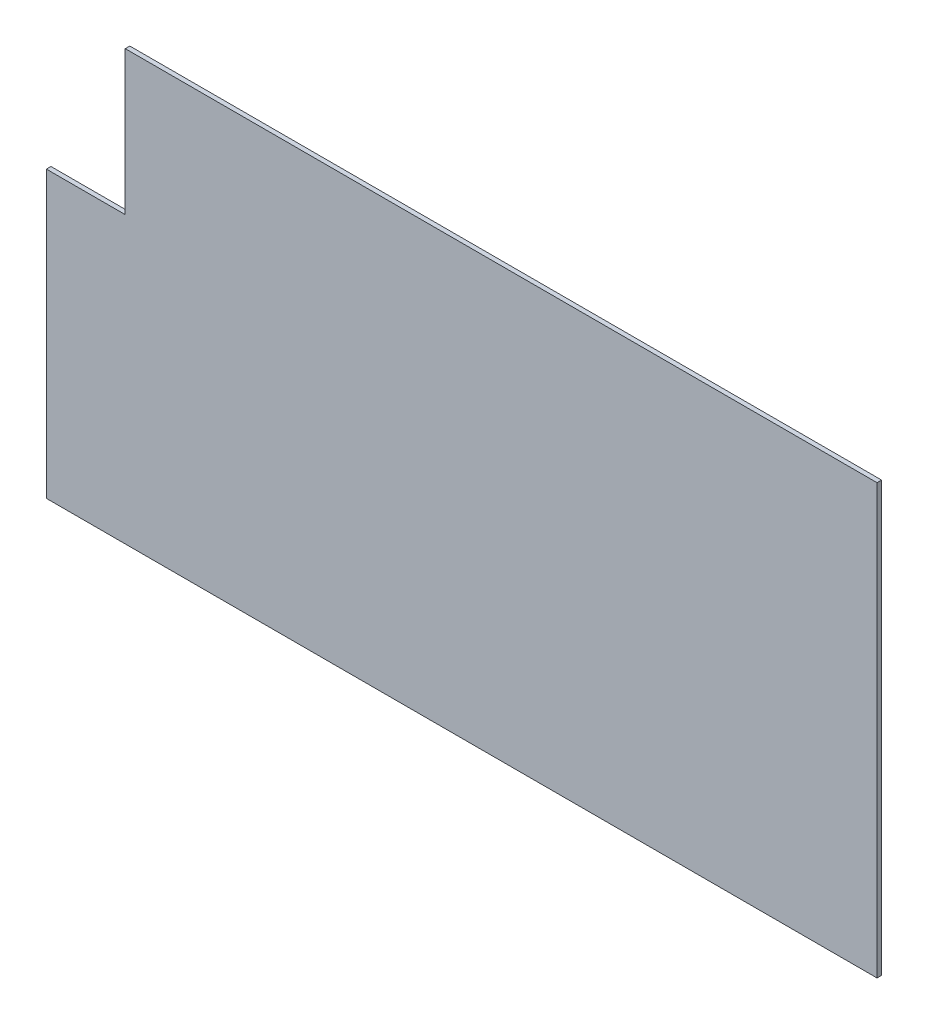
SolidWorks part; units mm, degrees
material "Acrylic (Medium-high impact)"
ref_plane "Front Plane" through (0, 0, 0) normal (0, 0, 1) x (1, 0, 0)
ref_plane "Top Plane" through (0, 0, 0) normal (0, 1, 0) x (1, 0, 0)
ref_plane "Right Plane" through (0, 0, 0) normal (1, 0, 0) x (0, 0, -1)
sketch "Sketch1" plane through (0, 0, 0) normal (0, 0, 1) x (1, 0, 0)
  line L1 (-289.5, -149.5) -> (289.5, -149.5)
  line L2 (-289.5, -149.5) -> (-289.5, 149.5)
  line L3 (-289.5, 149.5) -> (289.5, 149.5)
  line L4 (289.5, -149.5) -> (289.5, 149.5)
  line L5 (-289.5, -149.5) -> (289.5, 149.5) construction
  line L6 (-289.5, 149.5) -> (289.5, -149.5) construction
  point P0 (0, 0)
  dimension "D1" = 579
  dimension "D2" = 299
extrude "Boss-Extrude1" add sketch "Sketch1" along normal mid plane 3.175
sketch "Sketch2" plane through (0, 0, -1.5875) normal (0, 0, -1) x (-1, 0, 0)
  line L0 (236.25, 50.3) -> (284.75, 50.3) construction
  line L1 (235.55, 50.3) -> (289.5, 50.3) construction
  line L2 (235.55, 51) -> (235.55, 149) construction
  line L3 (235.55, 50.3) -> (235.55, 149.5) construction
  line L4 (289.5, 49.3) -> (289.5, 149.5)
  line L5 (289.5, 149.5) -> (289.5, -149.5) construction
  line L6 (289.5, 149.5) -> (234.55, 149.5)
  line L7 (234.55, 49.3) -> (234.55, 149.5)
  line L10 (234.55, 49.3) -> (289.5, 49.3)
  line L11 (289.5, 50.3) -> (289.5, 149.5) construction
  line L12 (289.5, 149.5) -> (235.55, 149.5) construction
  line L13 (234.55, 49.3) -> (234.55, 150.5) construction
  line L14 (234.55, 49.3) -> (290.5, 49.3) construction
  line L15 (290.5, 49.3) -> (290.5, 150.5) construction
  line L16 (290.5, 150.5) -> (234.55, 150.5) construction
  dimension "D1" = 1
extrude "Cut-Extrude1" cut sketch "Sketch2" against normal up to surface (3.175 mm away) up to face at (0, 0, 1.5875)
